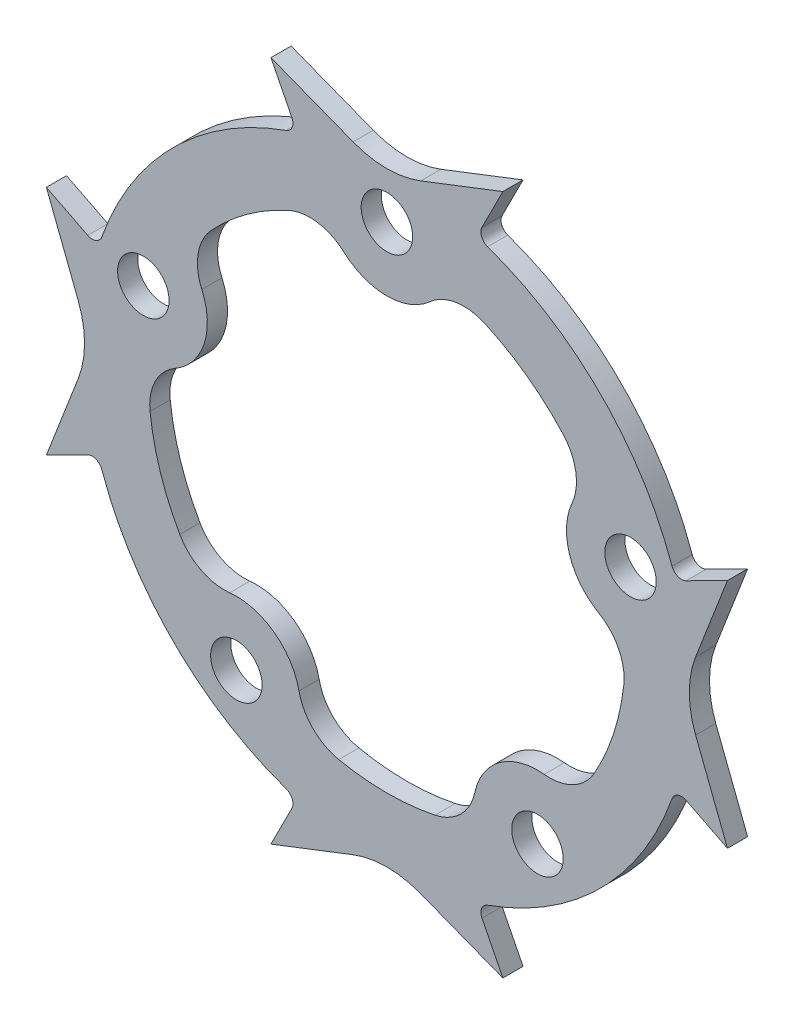
SolidWorks part; units mm, degrees
ref_plane "Front Plane" through (0, 0, 0) normal (0, 0, 1) x (1, 0, 0)
ref_plane "Top Plane" through (0, 0, 0) normal (0, 1, 0) x (1, 0, 0)
ref_plane "Right Plane" through (0, 0, 0) normal (1, 0, 0) x (0, 0, -1)
sketch "Sketch1" plane through (0, 0, 0) normal (0, 0, 1) x (1, 0, 0)
  line L0 (0, 25.4) -> (0, 0) construction
  line L1 (0, -23.6347) -> (0, -29.9847) construction
  line L2 (0, 0) -> (-11.5, 33.7706) construction
  line L3 (-11.5, 33.7706) -> (-8.9038, 28.6322)
  line L4 (-11.5, 33.7706) -> (-3.3557, 30.6125)
  line L5 (-11.5, 33.7706) -> (-3.7663, 36.4042) construction
  line L6 (0, 0) -> (0, 35.675) construction
  line L7 (11.5, 33.7706) -> (3.3557, 30.6125)
  line L8 (11.5, 33.7706) -> (8.9038, 28.6322)
  line L9 (-9.6657, 28.3841) -> (47321.284, 16146.1136) construction
  circle A0 centre (0, 0) radius 29.9847
  circle A1 centre (0, 25.4) radius 2.5527
  arc A2 (4.2487, 20.6808) -> (-4.2487, 20.6808) centre (0, 25.4) cw
  arc A3 (-23.4901, -2.6103) -> (-20.5382, -11.6953) centre (0, 0) ccw
  arc A4 (4.2487, 20.6808) -> (9.7414, 21.5338) centre (7.6476, 16.9054) cw
  arc A5 (-4.2487, 20.6808) -> (-9.7414, 21.5338) centre (-7.6476, 16.9054) ccw
  arc A6 (20.9815, 2.35) -> (18.3557, 10.4314) centre (24.1568, 7.849) cw
  circle A7 centre (24.1568, 7.849) radius 2.5527
  arc A8 (18.3557, 10.4314) -> (17.4696, 15.9189) centre (13.7147, 12.4973) ccw
  arc A9 (20.9815, 2.35) -> (23.4901, -2.6103) centre (18.4412, -2.0493) cw
  arc A10 (8.7186, -19.2284) -> (15.5931, -14.2338) centre (14.9297, -20.549) cw
  circle A11 centre (14.9297, -20.549) radius 2.5527
  arc A12 (15.5931, -14.2338) -> (20.5382, -11.6953) centre (16.1238, -9.1816) ccw
  arc A13 (8.7186, -19.2284) -> (4.7763, -23.1471) centre (3.7497, -18.1719) cw
  arc A14 (-15.5931, -14.2338) -> (-8.7186, -19.2284) centre (-14.9297, -20.549) cw
  circle A15 centre (-14.9297, -20.549) radius 2.5527
  arc A16 (-8.7186, -19.2284) -> (-4.7763, -23.1471) centre (-3.7497, -18.1719) ccw
  arc A17 (-15.5931, -14.2338) -> (-20.5382, -11.6953) centre (-16.1238, -9.1816) cw
  arc A18 (-18.3557, 10.4314) -> (-20.9815, 2.35) centre (-24.1568, 7.849) cw
  circle A19 centre (-24.1568, 7.849) radius 2.5527
  arc A20 (-20.9815, 2.35) -> (-23.4901, -2.6103) centre (-18.4412, -2.0493) ccw
  arc A21 (-18.3557, 10.4314) -> (-17.4696, 15.9189) centre (-13.7147, 12.4973) cw
  arc A22 (-4.7763, -23.1471) -> (4.7763, -23.1471) centre (0, 0) ccw
  arc A23 (20.5382, -11.6953) -> (23.4901, -2.6103) centre (0, 0) ccw
  arc A24 (17.4696, 15.9189) -> (9.7414, 21.5338) centre (0, 0) ccw
  arc A25 (-9.7414, 21.5338) -> (-17.4696, 15.9189) centre (0, 0) ccw
  circle A26 centre (0, 0) radius 35.675 construction
  arc A27 (-3.3557, 30.6125) -> (0, 29.9847) centre (0, 39.2664) ccw
  circle A28 centre (0, 25.4) radius 4.5847 construction
  arc A29 (3.3557, 30.6125) -> (0, 29.9847) centre (0, 39.2664) cw
  dimension "D2" = 5.1054
  dimension "D4" = 5.08
  dimension "D5" = 6.35
  dimension "D6" = 25.4
  dimension "D3" = 6.35
  dimension "D8" = 71.35
  dimension "D9" = 8
  dimension "D10" = 40
  dimension "D11" = 23
  dimension "D7" = 5
extrude "Boss-Extrude1" add sketch "Sketch1" along normal blind 2 contours A0 A25 A5 A2 A4 A24 A8 A6 A9 A23 A12 A10 A13 A22 A16 A14 A17 A3 A20 A18 A21 A19 A15 A11 A7 A1 region at (-4.3756, 28.8062, 0)
extrude "Boss-Extrude2" add sketch "Sketch1<4>" along normal up to surface (2 mm away) contours A27 L4 L3 A0 | L7 A29 A0 L8 region at (-7.4005, 30.8552, 0) region at (7.4005, 30.8552, 0) up to face at (0, 0, 2)
sketch "Sketch1<4>" plane through (0, 0, 0) normal (0, 0, 1) x (1, 0, 0) same geometry as "Sketch1"
fillet "Fillet1" radius 1 2 edges at (8.9038, 28.6322, 1) (-8.9038, 28.6322, 1)
pattern_circular "CirPattern1" count 4 over 360 about axis through (0, 0, 2) along (0, 0, 1) of "Fillet1", "Boss-Extrude2"
